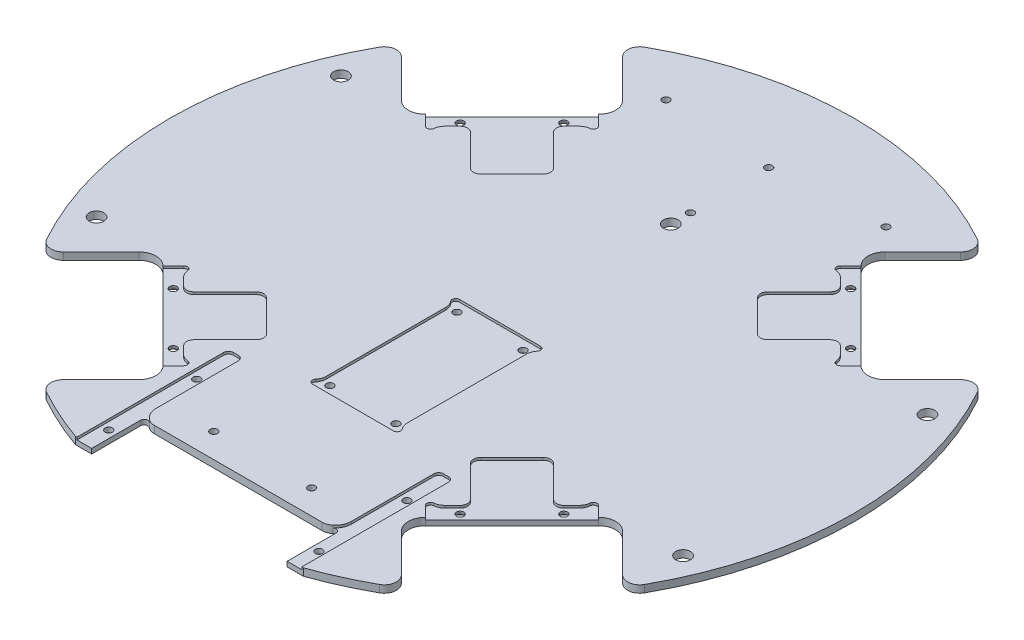
SolidWorks part; units mm, degrees
material "1060 Alloy"
ref_plane "Front Plane" through (0, 0, 0) normal (0, 0, 1) x (1, 0, 0)
ref_plane "Top Plane" through (0, 0, 0) normal (0, 1, 0) x (1, 0, 0)
ref_plane "Right Plane" through (0, 0, 0) normal (1, 0, 0) x (0, 0, -1)
sketch "Sketch1" plane through (0, 0, 0) normal (0, 1, 0) x (1, 0, 0)
  circle A0 centre (0, 0) radius 140
  dimension "D1" = 280
extrude "Boss-Extrude1" add sketch "Sketch1" along normal blind 3
sketch "Sketch7" plane through (0, 3, 0) normal (0, 1, 0) x (1, 0, 0)
  line L0 (-89.1308, -53.7048) -> (-53.7048, -89.1308)
  line L1 (-98.9596, -53.7048) -> (-121.6224, -76.3675)
  line L2 (-53.7048, -98.9596) -> (-76.3675, -121.6224)
  line L3 (-121.6224, -76.3675) -> (-76.3675, -121.6224)
  line L4 (0, 0) -> (-98.9949, -98.9949) construction
  line L7 (0, 0) -> (0, 130) construction
  circle A0 centre (0, 0) radius 140 construction
  arc A1 (-98.9596, -53.7048) -> (-89.1308, -53.7048) centre (-94.0452, -58.6192) cw
  arc A2 (-53.7048, -89.1308) -> (-53.7048, -98.9596) centre (-58.6192, -94.0452) cw
  dimension "D4" = 6.95
  dimension "D1" = 101
  dimension "D2" = 64
  dimension "D3" = 135
extrude "Cut-Extrude4" cut sketch "Sketch7" against normal up to next
sketch "Sketch8" plane through (0, 3, 0) normal (0, 1, 0) x (1, 0, 0)
  line L0 (-89.1308, -53.7048) -> (-53.7048, -89.1308)
  line L1 (-89.1308, -53.7048) -> (-84.8882, -49.4621)
  line L2 (-53.7048, -89.1308) -> (-49.4621, -84.8882)
  line L3 (-80.8907, -53.4596) -> (-53.4596, -80.8907)
  line L6 (-53.7048, -89.1308) -> (-89.1308, -53.7048) construction
  arc A0 (-84.8882, -49.4621) -> (-82.3339, -50.3846) centre (-83.8275, -50.5228) cw
  arc A1 (-82.3339, -50.3846) -> (-80.8907, -53.4596) centre (-77.3551, -49.9241) ccw
  arc A2 (-49.4621, -84.8882) -> (-50.3846, -82.3339) centre (-50.5228, -83.8275) ccw
  arc A3 (-50.3846, -82.3339) -> (-53.4596, -80.8907) centre (-49.9241, -77.3551) cw
  dimension "D2" = 1.5
  dimension "D3" = 5
  dimension "D4" = 1.5
  dimension "D5" = 5
  dimension "D1" = 6
extrude "Cut-Extrude5" cut sketch "Sketch8" against normal blind 1
sketch "Sketch14" plane through (0, 3, 0) normal (0, 1, 0) x (1, 0, 0)
  line L0 (-53.4596, -80.8907) -> (-80.8907, -53.4596) construction
  line L1 (-53.4596, -80.8907) -> (-80.8907, -53.4596) construction
  line L2 (-73.5391, -56.5685) -> (-60.8112, -43.8406)
  line L3 (-56.5685, -73.5391) -> (-43.8406, -60.8112)
  line L4 (-56.5685, -43.8406) -> (-43.8406, -56.5685)
  line L5 (-77.7817, -56.5685) -> (-56.5685, -77.7817)
  line L8 (-84.8882, -49.4621) -> (-89.1308, -53.7048) construction
  arc A0 (-77.7817, -56.5685) -> (-73.5391, -56.5685) centre (-75.6604, -54.4472) ccw
  arc A1 (-56.5685, -77.7817) -> (-56.5685, -73.5391) centre (-54.4472, -75.6604) cw
  arc A2 (-60.8112, -43.8406) -> (-56.5685, -43.8406) centre (-58.6899, -45.9619) cw
  arc A3 (-43.8406, -60.8112) -> (-43.8406, -56.5685) centre (-45.9619, -58.6899) ccw
  dimension "D1" = 3
  dimension "D2" = 24
  dimension "D3" = 24
  dimension "D4" = 13.05
extrude "Cut-Extrude10" cut sketch "Sketch14" against normal up to surface (1 mm away) up to face at (-67.9432, 2, 67.9432)
sketch "Sketch9" plane through (0, 2, 0) normal (0, 1, 0) x (1, 0, 0)
  line L0 (-49.4621, -84.8882) -> (-84.8882, -49.4621) construction
  line L3 (-49.4621, -84.8882) -> (-84.8882, -49.4621) construction
  line L4 (-98.9596, -53.7048) -> (-119.0017, -73.7469) construction
  circle A0 centre (-79.9031, -58.6899) radius 1.5
  circle A1 centre (-58.6899, -79.9031) radius 1.5
  dimension "D4" = 3
  dimension "D1" = 3
  dimension "D2" = 30
  dimension "D3" = 17
  dimension "D5" = 3
extrude "Cut-Extrude6" cut sketch "Sketch9" against normal up to next
fillet "Fillet1" radius 5 2 edges at (-73.7469, 1.5, 119.0017) (-119.0017, 1.5, 73.7469)
pattern_circular "CirPattern1" count 4 over 360 about axis through (0, 3, 0) along (0, 1, 0) of "Cut-Extrude4", "Cut-Extrude6", "Fillet1", "Cut-Extrude5", "Cut-Extrude10"
sketch "Sketch2" plane through (0, 3, 0) normal (0, 1, 0) x (1, 0, 0)
  line L0 (-46.6476, -132) -> (-40, -132)
  line L1 (-40, -132) -> (-40, -112)
  line L2 (-34.3467, -112) -> (34.3467, -112)
  line L3 (40, -112) -> (40, -132)
  line L4 (40, -132) -> (46.6476, -132)
  line L5 (46.6476, -132) -> (46.6476, -140)
  line L6 (46.6476, -140) -> (-46.6476, -140)
  line L7 (-46.6476, -140) -> (-46.6476, -132)
  circle A0 centre (0, 0) radius 140 construction
  arc A1 (-40, -112) -> (-37.5415, -110.8462) centre (-38.5, -112) cw
  arc A2 (-34.3467, -112) -> (-37.5415, -110.8462) centre (-34.3467, -107) cw
  arc A3 (40, -112) -> (37.5415, -110.8462) centre (38.5, -112) ccw
  arc A4 (34.3467, -112) -> (37.5415, -110.8462) centre (34.3467, -107) ccw
  dimension "D5" = 1.5
  dimension "D6" = 5
  dimension "D1" = 8
  dimension "D2" = 20
  dimension "D3" = 80
  dimension "D4" = 6.6476
extrude "Cut-Extrude1" cut sketch "Sketch2" against normal up to next
sketch "Sketch3" plane through (0, 3, 0) normal (0, 1, 0) x (1, 0, 0)
  line L0 (-40, -132) -> (-46.6476, -132) construction
  line L1 (-40, -132) -> (-46, -132)
  line L2 (-40, -132) -> (-40, -72)
  line L3 (-42, -70) -> (-44, -70)
  line L4 (-46, -132) -> (-46, -72)
  line L5 (40, -132) -> (46, -132)
  line L6 (40, -132) -> (40, -72)
  line L7 (42, -70) -> (44, -70)
  line L8 (46, -132) -> (46, -72)
  line L12 (-40, -112) -> (-40, -132) construction
  line L13 (40, -132) -> (40, -112) construction
  arc A0 (40, -72) -> (42, -70) centre (42, -72) cw
  arc A1 (44, -70) -> (46, -72) centre (44, -72) cw
  arc A2 (-40, -72) -> (-42, -70) centre (-42, -72) ccw
  arc A3 (-44, -70) -> (-46, -72) centre (-44, -72) ccw
  dimension "D5" = 2
  dimension "D1" = 6
  dimension "D2" = 62
extrude "Cut-Extrude2" cut sketch "Sketch3" against normal blind 1
sketch "Sketch18" plane through (0, 3, 0) normal (0, 1, 0) x (1, 0, 0)
  line L0 (-40, -112) -> (-40, -72) construction
  line L1 (-40, -112) -> (-40, -72) construction
  line L3 (-40, -105.608) -> (-40, -112)
  line L4 (-40, -112) -> (-37.5415, -110.8462)
  line L5 (40, -72) -> (40, -112) construction
  line L6 (40, -105.608) -> (40, -112)
  line L7 (40, -112) -> (37.5415, -110.8462)
  arc A0 (-37.5415, -110.8462) -> (-40, -105.608) centre (-33.1904, -105.608) cw
  arc A2 (-37.5415, -110.8462) -> (-34.3467, -112) centre (-34.3467, -107) ccw construction
  arc A3 (37.5415, -110.8462) -> (40, -105.608) centre (33.1904, -105.608) ccw
  arc A4 (34.3467, -112) -> (37.5415, -110.8462) centre (34.3467, -107) ccw construction
extrude "Cut-Extrude14" cut sketch "Sketch18" against normal up to surface (1 mm away) up to face at (42.5714, 2, 94.1674)
fillet "Fillet3" radius 1.5 8 edges at (58.6899, 0, 81.4031) (79.9031, 0, 60.1899) (79.9031, 0, -57.1899) (58.6899, 0, -78.4031) (-58.6899, 0, -78.4031) (-79.9031, 0, -57.1899) (-58.6899, 0, 81.4031) (-79.9031, 0, 60.1899)
sketch "Sketch10" plane through (0, 3, 0) normal (0, 1, 0) x (1, 0, 0)
  circle A0 centre (-13.5, -61) radius 1.5
  circle A1 centre (13.5, -61) radius 1.5
  circle A2 centre (-13.5, -9) radius 1.5
  circle A3 centre (13.5, -9) radius 1.5
  dimension "D3" = 3
  dimension "D1" = 13.5
  dimension "D2" = 27
  dimension "D4" = 61
  dimension "D5" = 52
extrude "Cut-Extrude7" cut sketch "Sketch10" against normal up to next
sketch "Sketch11" plane through (0, 3, 0) normal (0, 1, 0) x (1, 0, 0)
  line L0 (34.3467, -112) -> (-34.3467, -112) construction
  circle A0 centre (-20, -102) radius 1.5
  circle A1 centre (20, -102) radius 1.5
  dimension "D1" = 3
  dimension "D2" = 40
  dimension "D3" = 10
  dimension "D4" = 20
extrude "Cut-Extrude8" cut sketch "Sketch11" against normal up to next
sketch "Sketch13" plane through (0, 3, 0) normal (0, 1, 0) x (1, 0, 0)
  line L0 (-46, -132) -> (-40, -132) construction
  line L4 (-40, -105.608) -> (-40, -72) construction
  line L5 (40, -72) -> (40, -105.608) construction
  circle A0 centre (-43, -86) radius 1.5
  circle A1 centre (-43, -122) radius 1.5
  circle A2 centre (43, -122) radius 1.5
  circle A3 centre (43, -86) radius 1.5
  dimension "D1" = 3
  dimension "D2" = 10
  dimension "D3" = 36
  dimension "D4" = 3
  dimension "D5" = 3
extrude "Cut-Extrude9" cut sketch "Sketch13" against normal up to next
sketch "Sketch15" plane through (0, 3, 0) normal (0, 1, 0) x (1, 0, 0)
  line L1 (-16.55, -4.95) -> (16.55, -4.95)
  line L2 (-16.55, -10.6033) -> (-16.55, -59.3967)
  line L3 (-16.55, -65.05) -> (16.55, -65.05)
  line L4 (16.55, -10.6033) -> (16.55, -59.3967)
  circle A0 centre (-13.5, -61) radius 1.5 construction
  circle A1 centre (-13.5, -9) radius 1.5 construction
  arc A2 (-16.55, -4.95) -> (-17.7038, -7.4085) centre (-16.55, -6.45) ccw
  arc A3 (-16.55, -10.6033) -> (-17.7038, -7.4085) centre (-21.55, -10.6033) ccw
  arc A4 (16.55, -4.95) -> (17.7038, -7.4085) centre (16.55, -6.45) cw
  arc A5 (17.7038, -7.4085) -> (16.55, -10.6033) centre (21.55, -10.6033) ccw
  arc A6 (-16.55, -65.05) -> (-17.7038, -62.5915) centre (-16.55, -63.55) cw
  arc A7 (-17.7038, -62.5915) -> (-16.55, -59.3967) centre (-21.55, -59.3967) ccw
  arc A8 (16.55, -65.05) -> (17.7038, -62.5915) centre (16.55, -63.55) ccw
  arc A9 (17.7038, -62.5915) -> (16.55, -59.3967) centre (21.55, -59.3967) cw
  dimension "D3" = 4.05
  dimension "D5" = 1.5
  dimension "D6" = 5
  dimension "D1" = 33.1
  dimension "D2" = 4.05
  dimension "D4" = 16.55
extrude "Cut-Extrude11" cut sketch "Sketch15" against normal blind 1
sketch "Sketch16" plane through (0, 3, 0) normal (0, 1, 0) x (1, 0, 0)
  circle A0 centre (0, 73) radius 1.5
  circle A1 centre (-45, 108) radius 1.5
  circle A2 centre (45, 108) radius 1.5
  circle A3 centre (0, 105) radius 1.5
  circle A4 centre (0, 65) radius 3
  dimension "D2" = 3
  dimension "D5" = 6
  dimension "D1" = 73
  dimension "D3" = 108
  dimension "D4" = 90
  dimension "D6" = 32
  dimension "D7" = 65
extrude "Cut-Extrude12" cut sketch "Sketch16" against normal up to next
sketch "Sketch17" plane through (0, 3, 0) normal (0, 1, 0) x (1, 0, 0)
  circle A0 centre (-120, 50) radius 3
  circle A1 centre (-120, -50) radius 3
  circle A2 centre (120, 50) radius 3
  circle A3 centre (120, -50) radius 3
  dimension "D1" = 6
  dimension "D2" = 50
  dimension "D3" = 50
  dimension "D4" = 120
  dimension "D5" = 120
extrude "Cut-Extrude13" cut sketch "Sketch17" against normal up to next
